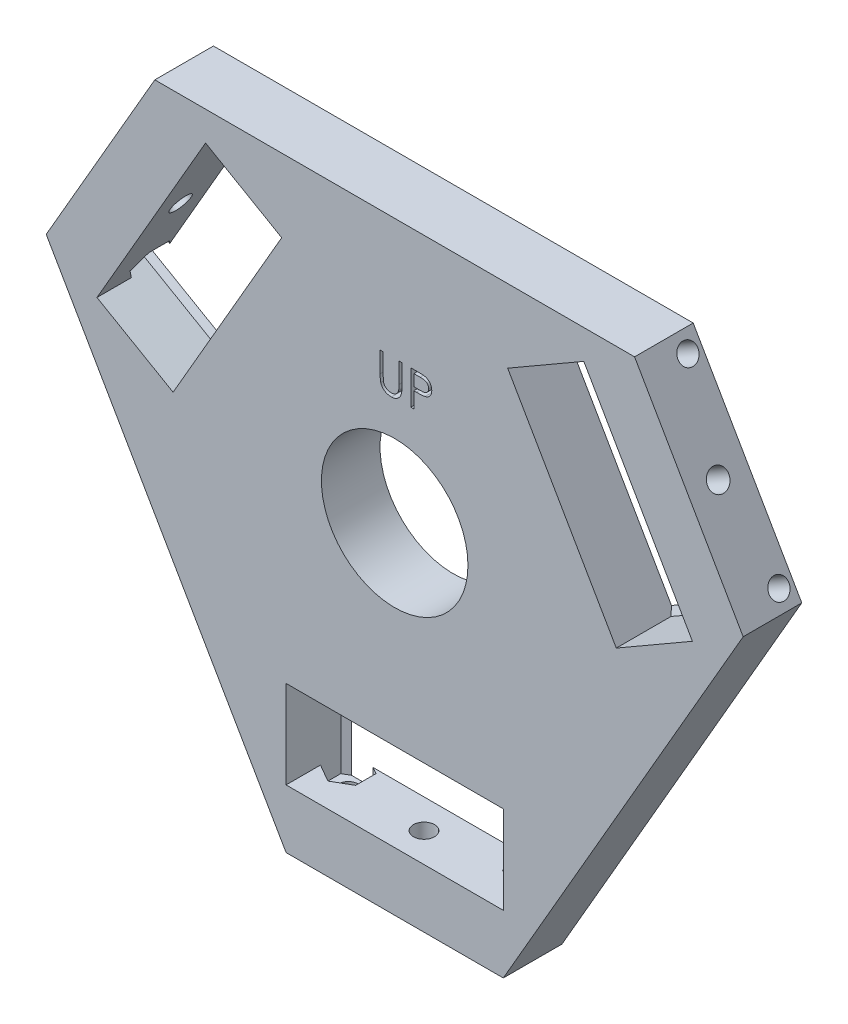
SolidWorks part; units mm, degrees
ref_plane "Plano frontal" through (0, 0, 0) normal (0, 0, 1) x (1, 0, 0)
ref_plane "Plano superior" through (0, 0, 0) normal (0, 1, 0) x (1, 0, 0)
ref_plane "Plano direito" through (0, 0, 0) normal (1, 0, 0) x (0, 0, -1)
sketch "Esboço1" plane through (0, 0, 0) normal (0, 0, 1) x (1, 0, 0)
  line L0 (0, 0) -> (0, -60) construction
  line L1 (-42.4264, 42.4264) -> (-57.9555, 15.5291)
  line L2 (-57.9555, 15.5291) -> (-15.5291, -57.9555)
  line L3 (-15.5291, -57.9555) -> (15.5291, -57.9555)
  line L4 (15.5291, -57.9555) -> (57.9555, 15.5291)
  line L5 (57.9555, 15.5291) -> (42.4264, 42.4264)
  line L6 (42.4264, 42.4264) -> (-42.4264, 42.4264)
  line L7 (0, 0) -> (60, 0) construction
  line L11 (-57.9555, 15.5291) -> (-59.4555, 12.9311)
  line L12 (-59.4555, 12.9311) -> (-18.5291, -57.9555)
  line L13 (-15.5291, -57.9555) -> (-18.5291, -57.9555)
  line L14 (42.4264, 42.4264) -> (40.9264, 45.0245)
  line L15 (42.4264, 42.4264) -> (-42.4264, 42.4264)
  line L16 (40.9264, 45.0245) -> (-40.9264, 45.0245)
  line L17 (-42.4264, 42.4264) -> (-40.9264, 45.0245)
  line L18 (15.5291, -57.9555) -> (18.5291, -57.9555)
  line L19 (15.5291, -57.9555) -> (57.9555, 15.5291)
  line L21 (18.5291, -57.9555) -> (59.4555, 12.9311)
  line L22 (57.9555, 15.5291) -> (59.4555, 12.9311)
  circle A0 centre (0, 0) radius 60 construction
  circle A1 centre (0, 0) radius 12.5
  point P3 (0, -60)
  point P4 (-51.9615, 30)
  point P5 (51.9615, 30)
  point P6 (15.5291, -57.9555)
  point P7 (-15.5291, -57.9555)
  point P12 (-57.9555, 15.5291)
  point P13 (-42.4264, 42.4264)
  point P14 (42.4264, 42.4264)
  point P15 (57.9555, 15.5291)
  point P21 (2.8357, -42.5904)
  point P23 (42.4264, 42.4264)
  dimension "D1" = 120
  dimension "D4" = 15
  dimension "D11" = 25
  dimension "D2" = 120
  dimension "D3" = 120
  dimension "D6" = 3
  dimension "D7" = 3
  dimension "D8" = 3
  dimension "D5" = 3
extrude "Ressalto-extrusão1" add sketch "Esboço1" along normal blind 10 contours L5 L6 L1 L2 L3 L4 | L1 | L5 L16 | L3 L21 | L13 L2 L11 L12 | L22 L4 L18 L21 | L16 L17 L15 L14 region at (0, 40.893, 0) region at (-37.8606, -21.8588, 0) region at (37.8606, -21.8588, 0)
ref_plane "Topo" through (0, 0, 10) normal (0, 0, 1) x (1, 0, 0)
sketch "Esboço2" plane through (0, -57.9555, 0) normal (0, -1, 0) x (1, 0, 0)
  line L0 (0, 0) -> (0, 10) construction
  line L1 (-12.8291, 3.9588) -> (-15.5291, 5.5177) construction
  line L2 (-15.5291, 5.5177) -> (-18.2291, 3.9588) construction
  line L3 (-18.2291, 3.9588) -> (-18.2291, 0.8412) construction
  line L4 (-18.5291, 0) -> (18.5291, 0)
  line L5 (18.5291, 0) -> (18.5291, 10)
  line L6 (18.5291, 10) -> (-18.5291, 10)
  line L7 (-18.5291, 10) -> (-18.5291, 0)
  line L8 (-18.5291, 0) -> (18.5291, 0)
  line L9 (18.5291, 0) -> (18.5291, 10)
  line L10 (18.5291, 10) -> (-18.5291, 10)
  line L11 (-18.5291, 10) -> (-18.5291, 0)
  line L12 (-18.2291, 0.8412) -> (-15.5291, -0.7177) construction
  line L13 (-15.5291, -0.7177) -> (-12.8291, 0.8412) construction
  line L14 (-12.8291, 0.8412) -> (-12.8291, 3.9588) construction
  line L21 (-12.5291, 4.1321) -> (-15.5291, 5.8641)
  line L22 (-15.5291, 5.8641) -> (-18.5291, 4.1321)
  line L23 (-18.5291, 4.1321) -> (-18.5291, 0.6679)
  line L24 (-18.5291, 0.6679) -> (-15.5291, -1.0641)
  line L25 (-15.5291, -1.0641) -> (-12.5291, 0.6679)
  line L26 (-12.5291, 0.6679) -> (-12.5291, 4.1321)
  line L27 (12.5291, 0.6679) -> (12.5291, 4.1321)
  line L28 (15.5291, -1.0641) -> (12.5291, 0.6679)
  line L29 (18.5291, 0.6679) -> (15.5291, -1.0641)
  line L30 (18.5291, 4.1321) -> (18.5291, 0.6679)
  line L31 (15.5291, 5.8641) -> (18.5291, 4.1321)
  line L32 (12.5291, 4.1321) -> (15.5291, 5.8641)
  circle A0 centre (-15.5291, 2.4) radius 1.5 construction
  circle A2 centre (-15.5291, 2.4) radius 2.7 construction
  circle A3 centre (-15.5291, 2.4) radius 1.7
  circle A4 centre (15.5291, 2.4) radius 1.7
  circle A5 centre (0, 5) radius 1.5 construction
  circle A6 centre (0, 5) radius 1.8
  point P35 (0, 0)
  point P36 (0, 10)
  point P37 (0, 0)
  point P38 (0, 0)
  line M5 (-18.5291, 0) -> (18.5291, 0)
  line M6 (18.5291, 0) -> (18.5291, 10)
  line M7 (18.5291, 10) -> (-18.5291, 10)
  line M8 (-18.5291, 10) -> (-18.5291, 0)
  dimension "D3" = 3
  dimension "D4" = 0.3
  dimension "D6" = 3
  dimension "D2" = 3
  dimension "D5" = 0.2
  dimension "D7" = 7.6
  dimension "D8" = 5.4
  dimension "D1" = 0
  dimension "D9" = 0.3
extrude "Corte-extrusão6" cut sketch "Esboço2" against normal blind 15 contours A3 | A4 | A6 region at (-15.5291, -57.9555, 2.4) region at (15.5291, -57.9555, 2.4) region at (0, -57.9555, 5)
extrude "Corte-extrusão7" cut sketch "Esboço2<3>" against normal blind 15 from offset 10 contours L27 L32 L31 L22 L21 L26 L25 L24 L29 L28 M6 M7 M8 M5 | L25 L26 L21 L22 L11 L24 A3 | A3 | A4 | L32 L27 L28 L29 L9 L31 A4 | A6 region at (-17.9087, -57.9555, 0.4066) region at (-12.9157, -57.9555, 0.0016) region at (13.1496, -57.9555, 0.4066) region at (-15.5291, -57.9555, 2.4) region at (15.5291, -57.9555, 2.4) region at (0, -57.9555, 5) offset against normal yes
sketch "Esboço2<3>" plane through (0, -57.9555, 0) normal (0, -1, 0) x (1, 0, 0) same geometry as "Esboço2"
extrude "Corte-extrusão8" cut sketch "Esboço2<4>" along normal blind 3 from offset 10 contours L25 L26 L21 L22 L11 L24 A3 | L32 L27 L28 L29 L9 L31 A4 | A4 | A3 region at (-17.9087, -57.9555, 0.4066) region at (13.1496, -57.9555, 0.4066) region at (-15.5291, -57.9555, 2.4) region at (15.5291, -57.9555, 2.4) offset against normal yes
sketch "Esboço2<4>" plane through (0, -57.9555, 0) normal (0, -1, 0) x (1, 0, 0) same geometry as "Esboço2"
pattern_circular "PadrãoCircular1" count 3 over 360 about axis through (0, 0, 10) along (0, 0, 1) of "Corte-extrusão8", "Corte-extrusão7", "Corte-extrusão6"
sketch "Esboço3" plane through (0, 0, 10) normal (0, 0, 1) x (1, 0, 0)
  text T0 "UP" font "Century Gothic" height in points 22
extrude "Corte-extrusão9" cut sketch "Esboço3" against normal blind 3
